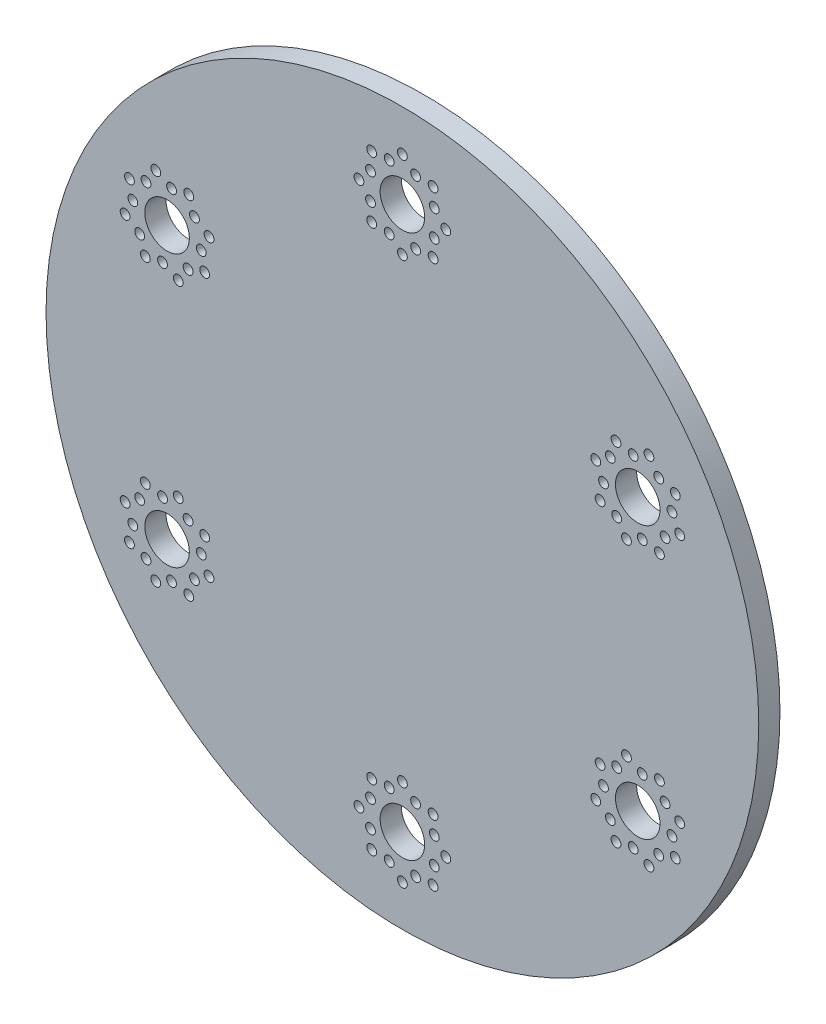
SolidWorks part; units mm, degrees
ref_plane "Front Plane" through (0, 0, 0) normal (0, 0, 1) x (1, 0, 0)
ref_plane "Top Plane" through (0, 0, 0) normal (0, 1, 0) x (1, 0, 0)
ref_plane "Right Plane" through (0, 0, 0) normal (1, 0, 0) x (0, 0, -1)
sketch "Sketch1" plane through (0, 0, 0) normal (0, 0, 1) x (1, 0, 0)
  circle A0 centre (0, 0) radius 80
  circle A2 centre (6.8943, 67.8943) radius 1.1
  circle A3 centre (0, 70.75) radius 1.1
  circle A4 centre (9.75, 61) radius 1.1
  circle A5 centre (6.8943, 54.1057) radius 1.1
  circle A6 centre (0, 51.25) radius 1.1
  circle A7 centre (-6.8943, 54.1057) radius 1.1
  circle A8 centre (-9.75, 61) radius 1.1
  circle A9 centre (-6.8943, 67.8943) radius 1.1
  circle A10 centre (0, 61) radius 5
  circle A11 centre (7.1601, 63.9658) radius 1.1
  circle A12 centre (2.9658, 68.1601) radius 1.1
  circle A13 centre (7.1601, 58.0342) radius 1.1
  circle A14 centre (2.9658, 53.8399) radius 1.1
  circle A15 centre (-2.9658, 53.8399) radius 1.1
  circle A16 centre (-7.1601, 58.0342) radius 1.1
  circle A17 centre (-7.1601, 63.9658) radius 1.1
  circle A18 centre (-2.9658, 68.1601) radius 1.1
  circle A20 centre (62.2453, 27.9765) radius 1.1
  circle A21 centre (61.2713, 35.375) radius 1.1
  circle A22 centre (57.7025, 22.0563) radius 1.1
  circle A23 centre (50.3041, 21.0822) radius 1.1
  circle A24 centre (44.3838, 25.625) radius 1.1
  circle A25 centre (43.4098, 33.0235) radius 1.1
  circle A26 centre (47.9525, 38.9437) radius 1.1
  circle A27 centre (55.351, 39.9178) radius 1.1
  circle A28 centre (52.8275, 30.5) radius 5
  circle A29 centre (58.976, 25.7821) radius 1.1
  circle A30 centre (60.5112, 31.5116) radius 1.1
  circle A31 centre (53.8391, 22.8163) radius 1.1
  circle A32 centre (48.1096, 24.3515) radius 1.1
  circle A33 centre (45.1439, 29.4884) radius 1.1
  circle A34 centre (46.6791, 35.2179) radius 1.1
  circle A35 centre (51.816, 38.1837) radius 1.1
  circle A36 centre (57.5455, 36.6485) radius 1.1
  circle A38 centre (55.351, -39.9178) radius 1.1
  circle A39 centre (61.2713, -35.375) radius 1.1
  circle A40 centre (47.9525, -38.9437) radius 1.1
  circle A41 centre (43.4098, -33.0235) radius 1.1
  circle A42 centre (44.3838, -25.625) radius 1.1
  circle A43 centre (50.3041, -21.0822) radius 1.1
  circle A44 centre (57.7025, -22.0563) radius 1.1
  circle A45 centre (62.2453, -27.9765) radius 1.1
  circle A46 centre (52.8275, -30.5) radius 5
  circle A47 centre (51.816, -38.1837) radius 1.1
  circle A48 centre (57.5455, -36.6485) radius 1.1
  circle A49 centre (46.6791, -35.2179) radius 1.1
  circle A50 centre (45.1439, -29.4884) radius 1.1
  circle A51 centre (48.1096, -24.3515) radius 1.1
  circle A52 centre (53.8391, -22.8163) radius 1.1
  circle A53 centre (58.976, -25.7821) radius 1.1
  circle A54 centre (60.5112, -31.5116) radius 1.1
  circle A56 centre (-6.8943, -67.8943) radius 1.1
  circle A57 centre (0, -70.75) radius 1.1
  circle A58 centre (-9.75, -61) radius 1.1
  circle A59 centre (-6.8943, -54.1057) radius 1.1
  circle A60 centre (0, -51.25) radius 1.1
  circle A61 centre (6.8943, -54.1057) radius 1.1
  circle A62 centre (9.75, -61) radius 1.1
  circle A63 centre (6.8943, -67.8943) radius 1.1
  circle A64 centre (0, -61) radius 5
  circle A65 centre (-7.1601, -63.9658) radius 1.1
  circle A66 centre (-2.9658, -68.1601) radius 1.1
  circle A67 centre (-7.1601, -58.0342) radius 1.1
  circle A68 centre (-2.9658, -53.8399) radius 1.1
  circle A69 centre (2.9658, -53.8399) radius 1.1
  circle A70 centre (7.1601, -58.0342) radius 1.1
  circle A71 centre (7.1601, -63.9658) radius 1.1
  circle A72 centre (2.9658, -68.1601) radius 1.1
  circle A74 centre (-62.2453, -27.9765) radius 1.1
  circle A75 centre (-61.2713, -35.375) radius 1.1
  circle A76 centre (-57.7025, -22.0563) radius 1.1
  circle A77 centre (-50.3041, -21.0822) radius 1.1
  circle A78 centre (-44.3838, -25.625) radius 1.1
  circle A79 centre (-43.4098, -33.0235) radius 1.1
  circle A80 centre (-47.9525, -38.9437) radius 1.1
  circle A81 centre (-55.351, -39.9178) radius 1.1
  circle A82 centre (-52.8275, -30.5) radius 5
  circle A83 centre (-58.976, -25.7821) radius 1.1
  circle A84 centre (-60.5112, -31.5116) radius 1.1
  circle A85 centre (-53.8391, -22.8163) radius 1.1
  circle A86 centre (-48.1096, -24.3515) radius 1.1
  circle A87 centre (-45.1439, -29.4884) radius 1.1
  circle A88 centre (-46.6791, -35.2179) radius 1.1
  circle A89 centre (-51.816, -38.1837) radius 1.1
  circle A90 centre (-57.5455, -36.6485) radius 1.1
  circle A92 centre (-55.351, 39.9178) radius 1.1
  circle A93 centre (-61.2713, 35.375) radius 1.1
  circle A94 centre (-47.9525, 38.9437) radius 1.1
  circle A95 centre (-43.4098, 33.0235) radius 1.1
  circle A96 centre (-44.3838, 25.625) radius 1.1
  circle A97 centre (-50.3041, 21.0822) radius 1.1
  circle A98 centre (-57.7025, 22.0563) radius 1.1
  circle A99 centre (-62.2453, 27.9765) radius 1.1
  circle A100 centre (-52.8275, 30.5) radius 5
  circle A101 centre (-51.816, 38.1837) radius 1.1
  circle A102 centre (-57.5455, 36.6485) radius 1.1
  circle A103 centre (-46.6791, 35.2179) radius 1.1
  circle A104 centre (-45.1439, 29.4884) radius 1.1
  circle A105 centre (-48.1096, 24.3515) radius 1.1
  circle A106 centre (-53.8391, 22.8163) radius 1.1
  circle A107 centre (-58.976, 25.7821) radius 1.1
  circle A108 centre (-60.5112, 31.5116) radius 1.1
  point P24 (0, 61)
  point P41 (0, 61)
  point P61 (52.8275, 30.5)
  point P78 (52.8275, 30.5)
  point P98 (52.8275, -30.5)
  point P115 (52.8275, -30.5)
  point P135 (0, -61)
  point P152 (0, -61)
  point P172 (-52.8275, -30.5)
  point P189 (-52.8275, -30.5)
  point P209 (-52.8275, 30.5)
  point P226 (-52.8275, 30.5)
  point P227 (0, 0)
  dimension "D1" = 160
  dimension "D4" = 2.2
  dimension "D5" = 10
  dimension "D6" = 2.2
  dimension "D3" = 9.75
  dimension "D7" = 7.75
  dimension "D8" = 7.1601
  dimension "D10" = 51.25
  dimension "D13" = 6
  dimension "D14" = 61
  dimension "D15" = 52.8275
  dimension "D9" = 8
  dimension "D11" = 8
extrude "Boss-Extrude6" add sketch "Sketch1" along normal blind 1.5875 contours A90 A89 A88 A87 A86 A85 A84 A83 A82 A81 A80 A79 A78 A77 A76 A75 A74 | A108 A107 A106 A105 A104 A103 A102 A101 A100 A99 A98 A97 A96 A95 A94 A93 A92 | A18 A17 A16 A15 A14 A13 A12 A11 A10 A9 A8 A7 A6 A5 A4 A3 A2 | A36 A35 A34 A33 A32 A31 A30 A29 A28 A27 A26 A25 A24 A23 A22 A21 A20 | A54 A53 A52 A51 A50 A49 A48 A47 A46 A45 A44 A43 A42 A41 A40 A39 A38 | A72 A71 A70 A69 A68 A67 A66 A65 A64 A63 A62 A61 A60 A59 A58 A57 A56 region at (0, 0, 0)
extrude "Boss-Extrude9" add sketch "Sketch1<10>" against normal blind 3.175
sketch "Sketch1<10>" plane through (0, 0, 0) normal (0, 0, 1) x (1, 0, 0) same geometry as "Sketch1"
